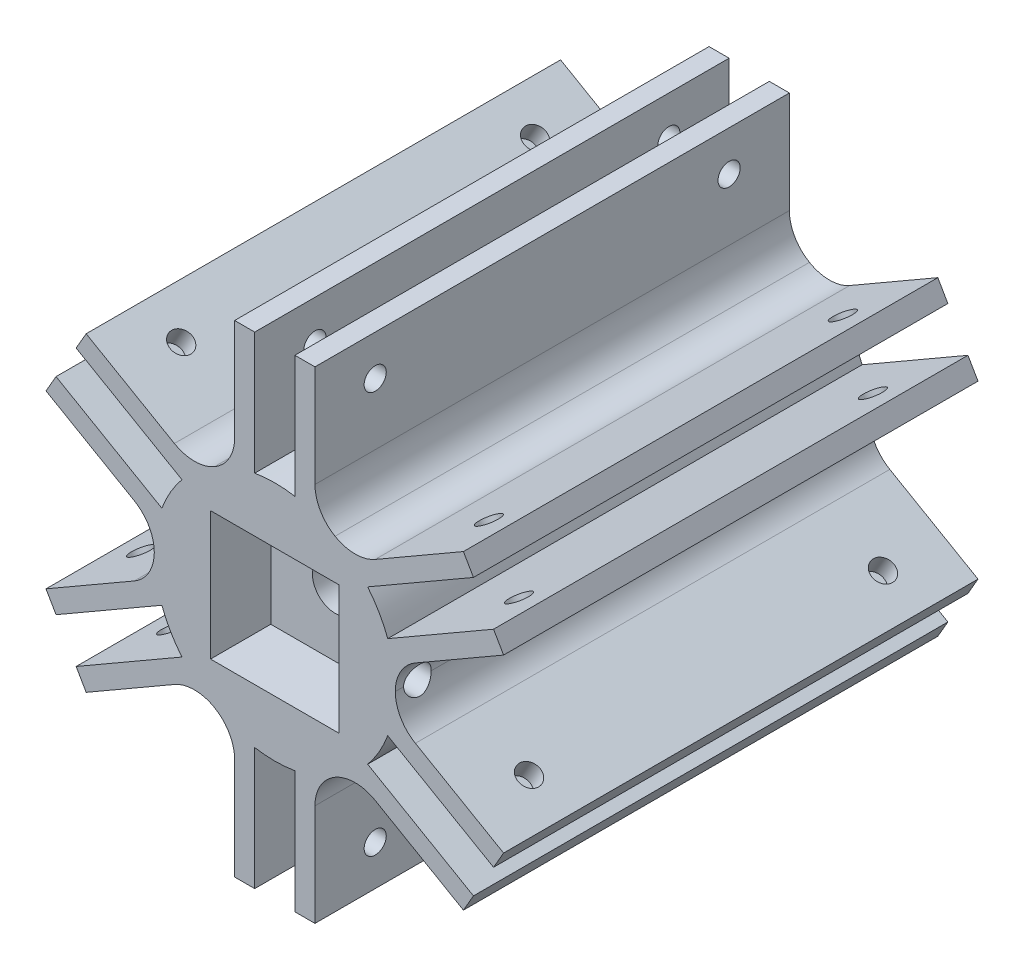
SolidWorks part; units mm, degrees
ref_plane "Front Plane" through (0, 0, 0) normal (0, 0, 1) x (1, 0, 0)
ref_plane "Top Plane" through (0, 0, 0) normal (0, 1, 0) x (1, 0, 0)
ref_plane "Right Plane" through (0, 0, 0) normal (1, 0, 0) x (0, 0, -1)
sketch "Sketch1" plane through (0, 0, 0) normal (0, 0, 1) x (1, 0, 0)
  line L6 (-6.35, -38.1) -> (6.35, -38.1)
  line L7 (-6.35, -38.1) -> (-6.35, 38.1)
  line L8 (-6.35, 38.1) -> (6.35, 38.1)
  line L9 (6.35, -38.1) -> (6.35, 38.1)
  line L10 (-6.35, -38.1) -> (6.35, 38.1) construction
  line L11 (-6.35, 38.1) -> (6.35, -38.1) construction
  line L12 (-3.175, -38.1) -> (3.175, -38.1)
  line L13 (-3.175, -38.1) -> (-3.175, 38.1)
  line L14 (-3.175, 38.1) -> (3.175, 38.1)
  line L15 (3.175, -38.1) -> (3.175, 38.1)
  line L16 (-3.175, -38.1) -> (3.175, 38.1) construction
  line L17 (-3.175, 38.1) -> (3.175, -38.1) construction
  circle A0 centre (0, 0) radius 120
  circle A1 centre (0, 0) radius 19.05
  dimension "D1" = 240
  dimension "D3" = 38.1
  dimension "D2" = 6.35
  dimension "D4" = 12.7
  dimension "D5" = 38.1
extrude "Boss-Extrude1" add sketch "Sketch1" along normal mid plane 75 contours L7 A1 | L13 A1 L7 | L15 A1 L13 | L9 A1 L15 | L9 A1 | A1 L13 L8 L7 | A1 L9 L8 L15 region at (-11.6105, 0, 0) region at (-4.7507, 0, 0) region at (0, 0, 0) region at (-4.7735, 28.2589, 0) region at (4.7507, 0, 0) region at (11.6105, 0, 0) region at (4.7735, 28.2589, 0)
sketch "Sketch5" plane through (6.35, 0, 0) normal (1, 0, 0) x (0, 0, -1)
  line L0 (-27.975, 31.75) -> (27.975, 31.75) construction
  line L1 (-37.5, 38.1) -> (37.5, 38.1) construction
  line L2 (-37.5, 17.9605) -> (-37.5, 38.1) construction
  circle A0 centre (-27.975, 31.75) radius 1.75
  circle A1 centre (27.975, 31.75) radius 1.75
  point P4 (0, 31.75)
  point P7 (0, 38.1)
  dimension "D1" = 3.5
  dimension "D2" = 12.7
  dimension "D3" = 9.525
extrude "Cut-Extrude4" cut sketch "Sketch5" against normal blind 12.7
pattern_circular "CirPattern1" count 6 over 360 about axis through (0, 0, 37.5) along (0, 0, 1) of "Boss-Extrude1", "Cut-Extrude4"
sketch "Sketch2" plane through (0, 0, 37.5) normal (0, 0, 1) x (1, 0, 0)
  line L1 (-10.16, 10.16) -> (10.16, 10.16)
  line L2 (-10.16, 10.16) -> (-10.16, -10.16)
  line L3 (-10.16, -10.16) -> (10.16, -10.16)
  line L4 (10.16, 10.16) -> (10.16, -10.16)
  line L5 (-10.16, 10.16) -> (10.16, -10.16) construction
  line L6 (-10.16, -10.16) -> (10.16, 10.16) construction
  point P0 (0, 0)
  point P6 (10.16, -10.16)
  point P7 (0, 0)
  dimension "D1" = 20.32
  dimension "D2" = 20.32
extrude "Cut-Extrude1" cut sketch "Sketch2" against normal blind 9.525
sketch "Sketch3" plane through (0, 0, 27.975) normal (0, 0, 1) x (1, 0, 0)
  circle A0 centre (0, 0) radius 3.5719
  dimension "D1" = 7.1437
extrude "Cut-Extrude2" cut sketch "Sketch3" against normal through all
sketch "Sketch4" plane through (10.16, 0, 0) normal (-1, 0, 0) x (0, 0, 1)
  line L1 (37.5, -10.16) -> (37.5, 10.16) construction
  circle A0 centre (34.0075, 0) radius 2.1828
  point P7 (0, 0)
  point P8 (0, 0)
  point P9 (0, 0)
  dimension "D1" = 4.3656
  dimension "D2" = 3.4925
  dimension "D3" = 10.16
extrude "Cut-Extrude3" cut sketch "Sketch4" against normal through all contours A0
fillet "Fillet1" radius 6.35 12 edges at (-12.3793, 14.4795, 0) (-6.35, 17.9605, 0) (6.35, 17.9605, 0) (12.3793, 14.4795, 0) (18.7293, -3.481, 0) (18.7293, 3.481, 0) (12.3793, -14.4795, 0) (6.35, -17.9605, 0) (-6.35, -17.9605, 0) (-12.3793, -14.4795, 0) (-18.7293, -3.481, 0) (-18.7293, 3.481, 0)
